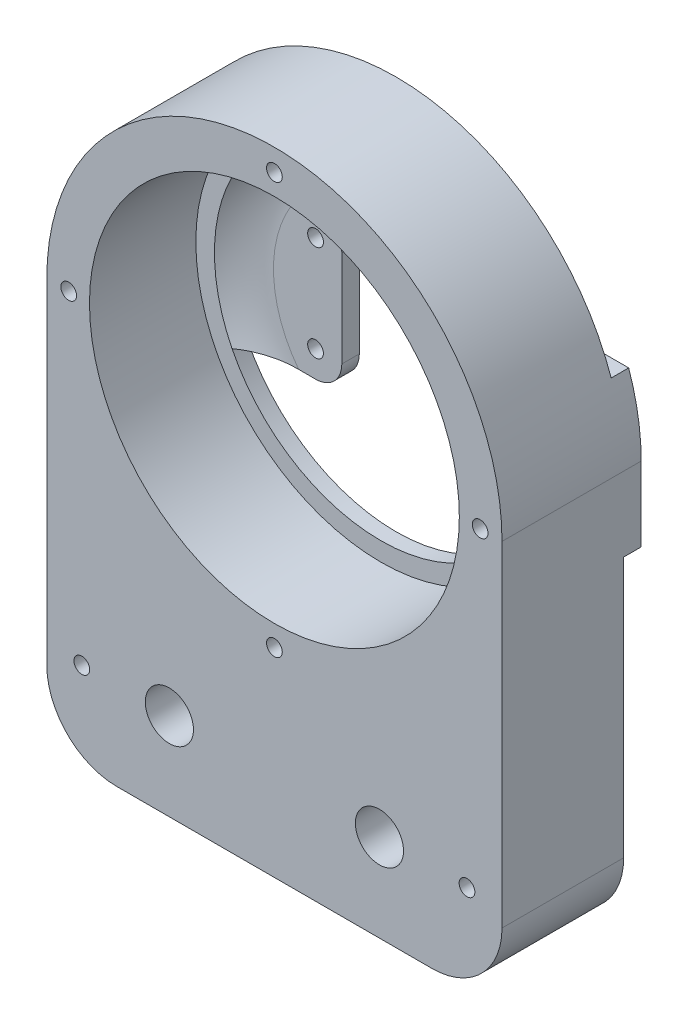
SolidWorks part; units mm, degrees
ref_plane "Спереди" through (0, 0, 0) normal (0, 0, 1) x (1, 0, 0)
ref_plane "Сверху" through (0, 0, 0) normal (0, 1, 0) x (1, 0, 0)
ref_plane "Справа" through (0, 0, 0) normal (1, 0, 0) x (0, 0, -1)
sketch "Эскиз2" plane through (0, 0, 0) normal (0, 0, 1) x (1, 0, 0)
  line L0 (0, 0) -> (0, 0.25)
  line L1 (-26, -10) -> (26, -10) construction
  line L2 (-26, 26.25) -> (26, 26.25)
  line L3 (-26, 26.25) -> (-26, -20)
  line L4 (-26, -20) -> (26, -20)
  line L5 (26, 26.25) -> (26, -20)
  line L6 (0, 26.25) -> (0, -20) construction
  circle A0 centre (0, 26.25) radius 26
  circle A1 centre (0, 26.25) radius 19
  circle A2 centre (-12, -10) radius 2.75
  circle A3 centre (12, -10) radius 2.75
  dimension "D1" = 52
  dimension "D4" = 38
  dimension "D6" = 5.5
  dimension "D2" = 0.25
  dimension "D3" = 20
  dimension "D5" = 10
  dimension "D7" = 24
extrude "Бобышка-Вытянуть1" add sketch "Эскиз2" along normal blind 13.9 contours A1 L2 A0 | A1 L2 A0 | A0 L3 L4 L5 A3 A2 region at (0, 45.8314, 0) region at (22.5, 25.6686, 0) region at (0, -6.3025, 0)
sketch "Эскиз3" plane through (0, 0, 13.9) normal (0, 0, 1) x (1, 0, 0)
  circle A0 centre (0, 26.25) radius 21.125
  dimension "D1" = 42.25
extrude "Вырез-Вытянуть1" cut sketch "Эскиз3" against normal blind 12.15
sketch "Эскиз4" plane through (0, 0, 0) normal (0, 0, -1) x (-1, 0, 0)
  circle A0 centre (-12, -10) radius 5
  circle A1 centre (12, -10) radius 5
  dimension "D1" = 10
  dimension "D2" = 10
extrude "Вырез-Вытянуть2" cut sketch "Эскиз4" against normal offset from surface (8.9 mm away) 5 up to face at (21.125, 26.25, 13.9)
fillet "Скругление1" radius 8 2 edges at (-26, -20, 6.95) (26, -20, 6.95)
sketch "Эскиз7" plane through (0, 0, 0) normal (0, 0, -1) x (-1, 0, 0)
  line L0 (-24.5713, 34.75) -> (-9.2, 34.75)
  line L1 (-9.2, 31.75) -> (9.2, 31.75) construction
  line L2 (-9.2, 31.75) -> (-9.2, 20.75) construction
  line L3 (-9.2, 20.75) -> (9.2, 20.75) construction
  line L4 (9.2, 31.75) -> (9.2, 20.75) construction
  line L5 (-9.2, 31.75) -> (9.2, 20.75) construction
  line L6 (-9.2, 20.75) -> (9.2, 31.75) construction
  line L7 (-6.2, 31.75) -> (-6.2, 20.75)
  line L8 (-9.2, 17.75) -> (-26, 17.75)
  line L9 (-26, 26.25) -> (-26, -12) construction
  line L10 (0, 0) -> (0, 26.25) construction
  line L11 (-26, 26.25) -> (-26, 17.75)
  line L12 (26, 26.25) -> (26, 17.75)
  line L13 (9.2, 17.75) -> (26, 17.75)
  line L14 (6.2, 31.75) -> (6.2, 20.75)
  line L15 (24.5713, 34.75) -> (9.2, 34.75)
  circle A0 centre (0, 26.25) radius 0.6921 construction
  circle A1 centre (0, 26.25) radius 19 construction
  arc A2 (26, 26.25) -> (-26, 26.25) centre (0, 26.25) ccw construction
  circle A3 centre (-9.2, 31.75) radius 0.9
  circle A4 centre (-9.2, 20.75) radius 0.9
  arc A5 (-9.2, 17.75) -> (-6.2, 20.75) centre (-9.2, 20.75) ccw
  arc A6 (-6.2, 31.75) -> (-9.2, 34.75) centre (-9.2, 31.75) ccw
  arc A7 (-26, 26.25) -> (-24.5713, 34.75) centre (0, 26.25) cw
  circle A8 centre (9.2, 20.75) radius 0.9
  circle A9 centre (9.2, 31.75) radius 0.9
  arc A10 (26, 26.25) -> (24.5713, 34.75) centre (0, 26.25) ccw
  arc A11 (9.2, 17.75) -> (6.2, 20.75) centre (9.2, 20.75) cw
  arc A12 (6.2, 31.75) -> (9.2, 34.75) centre (9.2, 31.75) cw
  point P0 (0, 26.25)
  point P27 (-24.5713, 34.75)
  point P29 (0, 0)
  point P30 (-26, 26.25)
  point P31 (-26, 17.75)
  dimension "D6" = 1.8
  dimension "D7" = 1.8
  dimension "D8" = 3
  dimension "D1" = 18.4
  dimension "D2" = 11
extrude "Бобышка-Вытянуть2" add sketch "Эскиз7" along normal blind 2
sketch "Эскиз5" plane through (0, 0, 13.9) normal (0, 0, 1) x (1, 0, 0)
  line L1 (-18, -20) -> (18, -20) construction
  line L2 (0, 26.25) -> (0, -20) construction
  circle A2 centre (0, 26.25) radius 23.5 construction
  circle A3 centre (0, 26.25) radius 21.125 construction
  circle A4 centre (0, 49.75) radius 0.9
  circle A5 centre (-23.5, 26.25) radius 0.9
  circle A6 centre (0, 2.75) radius 0.9
  circle A7 centre (23.5, 26.25) radius 0.9
  circle A8 centre (-22, -10) radius 0.9
  circle A9 centre (22, -10) radius 0.9
  dimension "D6" = 1.8
  dimension "D1" = 47
  dimension "D2" = 1.8
  dimension "D4" = 10
  dimension "D5" = 44
  dimension "D3" = 4
extrude "Вырез-Вытянуть3" cut sketch "Эскиз5" against normal through all
fillet "Скругление2" radius 8 2 edges at (19, 26.25, 0) (-19, 26.25, 0)
equation "\"big_bearing_d1\"= 19.9"
equation "\"big_bearing_d2\"= 42"
equation "\"big_bearing_h\"= 11.9"
equation "\"print_offset\"= 0.5"
equation "\"small_bearing_d1\"= 2.9"
equation "\"small_bearing_d2\"= 10"
equation "\"small_bearing_h\"= 4"
equation "\"tube_d\"= 16"
equation "\"small_bearing_distance\"= 2"
equation "\"D1@Эскиз2\"=\"big_bearing_d2\"+5*2"
equation "\"D2@Эскиз2\"=\"print_offset\"/2"
equation "\"D4@Эскиз2\"=\"big_bearing_d2\"-4"
equation "\"D1@Бобышка-Вытянуть1\"=\"big_bearing_h\"+2"
equation "\"D1@Эскиз3\"=\"big_bearing_d2\"+\"print_offset\"/2"
equation "\"D1@Вырез-Вытянуть1\"=\"big_bearing_h\"+\"print_offset\"/2"
equation "\"D2@Эскиз4\"=\"D1@Эскиз4\""
equation "\"D7@Эскиз7\"=1.8"
equation "\"D6@Эскиз5\"=\"D2@Эскиз5\""
